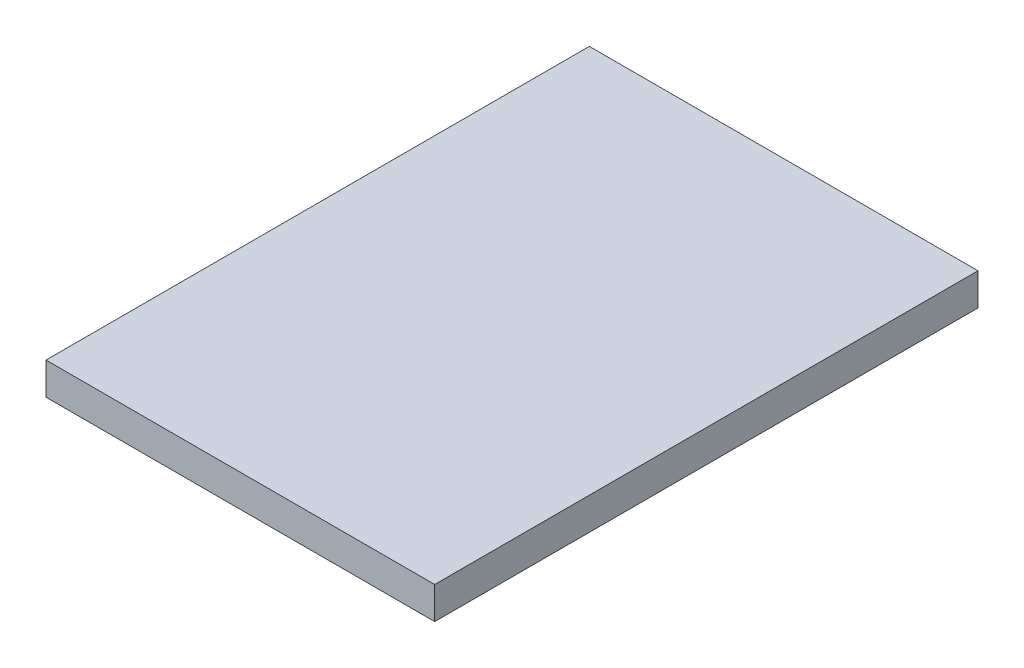
SolidWorks part; units mm, degrees
ref_plane "Front Plane" through (0, 0, 0) normal (0, 0, 1) x (1, 0, 0)
ref_plane "Top Plane" through (0, 0, 0) normal (0, 1, 0) x (1, 0, 0)
ref_plane "Right Plane" through (0, 0, 0) normal (1, 0, 0) x (0, 0, -1)
sketch "Sketch1" plane through (0, 0, 0) normal (0, 1, 0) x (1, 0, 0)
  line L1 (-9.3, -13) -> (9.3, -13)
  line L2 (-9.3, -13) -> (-9.3, 13)
  line L3 (-9.3, 13) -> (9.3, 13)
  line L4 (9.3, -13) -> (9.3, 13)
  line L5 (-9.3, -13) -> (9.3, 13) construction
  line L6 (-9.3, 13) -> (9.3, -13) construction
  point P0 (0, 0)
  dimension "D1" = 18.6
  dimension "D2" = 26
extrude "Boss-Extrude1" add sketch "Sketch1" along normal blind 1.54
sketch "Sketch2" plane through (0, 1.54, 0) normal (0, 1, 0) x (1, 0, 0)
  line L0 (-9.3, -13) -> (9.3, -13) construction
  line L1 (-5.25, -6) -> (5.25, -6)
  line L2 (-5.25, -6) -> (-5.25, -11)
  line L3 (-5.25, -11) -> (5.25, -11)
  line L4 (5.25, -6) -> (5.25, -11)
  line L5 (-5.25, -6) -> (5.25, -11) construction
  line L6 (-5.25, -11) -> (5.25, -6) construction
  line L7 (0, -8.5) -> (0, 0) construction
  point P0 (0, -8.5)
  dimension "D1" = 10.5
  dimension "D2" = 5
  dimension "D3" = 2
extrude "Boss-Extrude2" [suppressed] add sketch "Sketch2" along normal blind 8.5 separate body
sketch "Sketch3" plane through (0, 0, 0) normal (0, -1, 0) x (1, 0, 0)
  line L0 (-9.3, 13) -> (9.3, 13) construction
  line L1 (-6.75, 0.69) -> (6.75, 0.69)
  line L2 (-6.75, 0.69) -> (-6.75, 3.23)
  line L3 (-6.75, 3.23) -> (6.75, 3.23)
  line L4 (6.75, 0.69) -> (6.75, 3.23)
  line L5 (-6.75, 0.69) -> (6.75, 3.23) construction
  line L6 (-6.75, 3.23) -> (6.75, 0.69) construction
  line L7 (0, 1.96) -> (0, 0) construction
  point P0 (0, 1.96)
  dimension "D1" = 2.54
  dimension "D2" = 13.5
  dimension "D3" = 12.31
extrude "Boss-Extrude3" [suppressed] add sketch "Sketch3" along normal blind 2 and the other way offset from surface 7.8 separate body
sketch "Sketch4" plane through (0, 0, 0) normal (0, -1, 0) x (1, 0, 0)
  line L0 (-9.3, -13) -> (-9.3, 13) construction
  line L1 (-6.3, -6.45) -> (-8.84, -6.45)
  line L2 (-6.3, -6.45) -> (-6.3, -11.63)
  line L3 (-6.3, -11.63) -> (-8.84, -11.63)
  line L4 (-8.84, -6.45) -> (-8.84, -11.63)
  line L5 (-6.3, -6.45) -> (-8.84, -11.63) construction
  line L6 (-6.3, -11.63) -> (-8.84, -6.45) construction
  line L7 (9.3, -13) -> (-9.3, -13) construction
  point P0 (-7.57, -9.04)
  dimension "D1" = 2.54
  dimension "D2" = 5.18
  dimension "D3" = 3
  dimension "D4" = 6.55
extrude "Boss-Extrude4" [suppressed] add sketch "Sketch4" along normal up to surface and the other way up to surface separate body
ref_plane "Plane1" through (0, 0, 0) normal (1, 0, 0) x (0, 0, -1)
